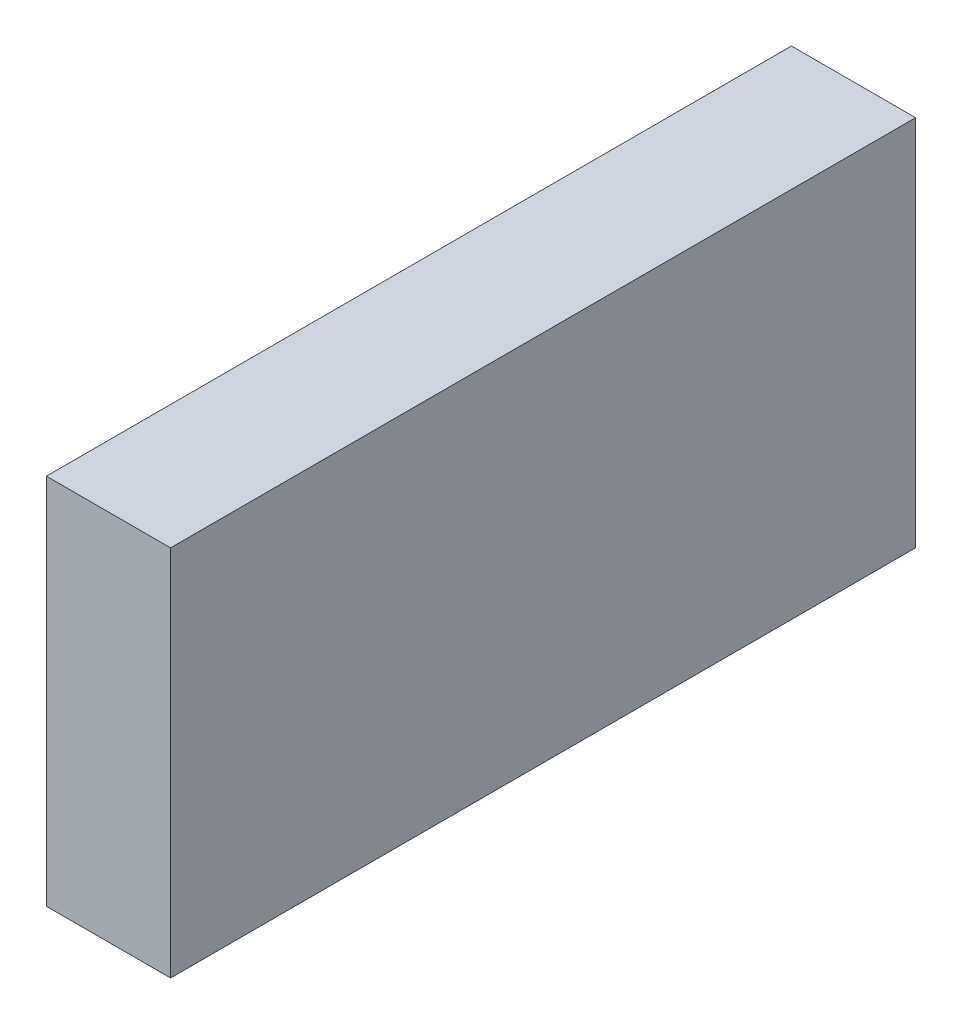
SolidWorks part; units mm, degrees
material "Maple"
ref_plane "Front Plane" through (0, 0, 0) normal (0, 0, 1) x (1, 0, 0)
ref_plane "Top Plane" through (0, 0, 0) normal (0, 1, 0) x (1, 0, 0)
ref_plane "Right Plane" through (0, 0, 0) normal (1, 0, 0) x (0, 0, -1)
sketch "Sketch1" plane through (0, 0, 0) normal (1, 0, 0) x (0, 0, -1)
  line L0 (0, 0) -> (76.2, 0)
  line L1 (0, 0) -> (0, 38.1)
  line L2 (76.2, 0) -> (76.2, 38.1)
  line L3 (0, 38.1) -> (76.2, 38.1)
  dimension "D1" = 76.2
  dimension "D2" = 38.1
extrude "Boss-Extrude1" add sketch "Sketch1" along normal blind 12.7
